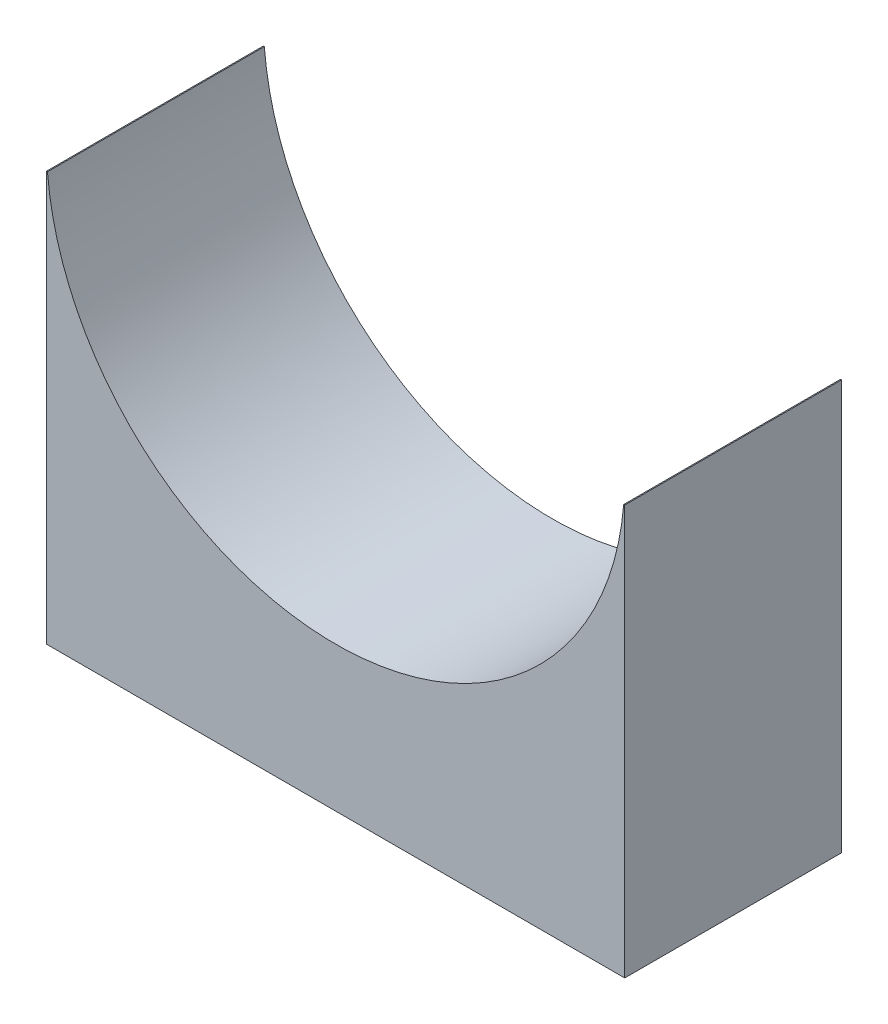
SolidWorks part; units mm, degrees
material "ABS"
ref_plane "Front Plane" through (0, 0, 0) normal (0, 0, 1) x (1, 0, 0)
ref_plane "Top Plane" through (0, 0, 0) normal (0, 1, 0) x (1, 0, 0)
ref_plane "Right Plane" through (0, 0, 0) normal (1, 0, 0) x (0, 0, -1)
ref_plane "Plane1" through (0, 0, 5) normal (0, 0, 1) x (1, 0, 0)
sketch "Sketch1" plane through (0, 0, 5) normal (0, 0, 1) x (1, 0, 0)
  line L0 (0, 25) -> (0, 0)
  line L1 (0, 0) -> (70, 0)
  line L2 (70, 0) -> (70, 25)
  line L3 (70, 25) -> (0, 25)
extrude "Boss-Extrude1" [suppressed] add sketch "Sketch1" against normal blind 5
sketch "Sketch2" [suppressed] plane through (0, 0, 5) normal (0, 0, 1) x (1, 0, 0)
  line L0 (38.9, 0) -> (38.9, 11)
  line L1 (21.1, 11) -> (21.1, 0)
  line L2 (21.1, 0) -> (38.9, 0)
  arc A0 (38.9, 11) -> (21.1, 11) centre (30, 11) ccw
extrude "Cut-Extrude1" [suppressed] cut sketch "Sketch2" against normal blind 0.5
sketch "Sketch3" [suppressed] plane through (0, 0, 0) normal (0, 0, -1) x (-1, 0, 0)
  line L0 (-36, 0) -> (-24, 0)
  line L1 (-24, 0) -> (-24, 11)
  line L2 (-36, 11) -> (-36, 0)
  arc A0 (-24, 11) -> (-36, 11) centre (-30, 11) ccw
extrude "Cut-Extrude2" [suppressed] cut sketch "Sketch3" against normal through all
sketch "Sketch4" [suppressed] plane through (0, 0, 0) normal (0, 0, -1) x (-1, 0, 0)
  line L0 (0, 8.5) -> (0, 13.5)
  line L1 (0, 13.5) -> (-9, 13.5)
  line L2 (-9, 8.5) -> (0, 8.5)
  arc A0 (-9, 13.5) -> (-9, 8.5) centre (-9, 11) ccw
extrude "Cut-Extrude3" [suppressed] cut sketch "Sketch4" against normal through all
sketch "Sketch5" [suppressed] plane through (0, 0, 0) normal (0, 0, -1) x (-1, 0, 0)
  line L0 (-52, 13.5) -> (-60, 13.5)
  line L1 (-60, 8.5) -> (-52, 8.5)
  arc A0 (-60, 13.5) -> (-60, 8.5) centre (-60, 11) ccw
  arc A1 (-52, 8.5) -> (-52, 13.5) centre (-52, 11) ccw
extrude "Cut-Extrude4" [suppressed] cut sketch "Sketch5" against normal through all
sketch "Sketch6" [suppressed] plane through (0, 0, 5) normal (0, 0, 1) x (1, 0, 0)
  line L0 (69, 5.5) -> (69, 19.5)
  line L1 (64.2, 19.5) -> (64.2, 5.5)
  arc A0 (64.2, 5.5) -> (69, 5.5) centre (66.6, 5.5) ccw
  arc A1 (69, 19.5) -> (64.2, 19.5) centre (66.6, 19.5) ccw
extrude "Cut-Extrude5" [suppressed] cut sketch "Sketch6" against normal blind 3
sketch "Sketch7" [suppressed] plane through (0, 0, 5) normal (0, 0, 1) x (1, 0, 0)
  line L0 (47.7, 5.5) -> (47.7, 19.5)
  line L1 (40.9, 19.5) -> (40.9, 5.5)
  arc A0 (40.9, 5.5) -> (47.7, 5.5) centre (44.3, 5.5) ccw
  arc A1 (47.7, 19.5) -> (40.9, 19.5) centre (44.3, 19.5) ccw
extrude "Cut-Extrude6" [suppressed] cut sketch "Sketch7" against normal blind 3
sketch "Sketch8" [suppressed] plane through (0, 0, 5) normal (0, 0, 1) x (1, 0, 0)
  line L0 (19.1, 5.5) -> (19.1, 19.5)
  line L1 (13.3, 19.5) -> (13.3, 5.5)
  arc A0 (13.3, 5.5) -> (19.1, 5.5) centre (16.2, 5.5) ccw
  arc A1 (19.1, 19.5) -> (13.3, 19.5) centre (16.2, 19.5) ccw
extrude "Cut-Extrude7" [suppressed] cut sketch "Sketch8" against normal blind 3
fillet "Fillet1" [suppressed] radius 1 tangent propagation no
sketch "Sketch9" plane through (0, 0, 0) normal (0, 0, 1) x (1, 0, 0)
  line L0 (-6, 0.5) -> (-5.9791, 0.5)
  line L1 (-6, 8) -> (6, 8)
  line L2 (-6, 8) -> (-6, -8)
  line L3 (-6, -8) -> (6, -8)
  line L4 (6, 8) -> (6, -8)
  line L5 (-6, -0.5) -> (-5.9791, -0.5)
  line L6 (5.9791, 0.5) -> (6, 0.5)
  line L7 (5.9791, -0.5) -> (6, -0.5)
  line L8 (-5.9896, 0.5) -> (-5.9896, -0.5) construction
  line L9 (-5.9896, 0) -> (-6, 0) construction
  line L10 (6, 8) -> (-6, -8) construction
  line L11 (-6, -8) -> (-6, -9)
  line L12 (-6, -9) -> (6, -9)
  line L13 (6, -9) -> (6, -8)
  line L14 (-6, 8) -> (-6, 9)
  line L15 (-6, 9) -> (6, 9)
  line L16 (6, 9) -> (6, 8)
  circle A0 centre (0, 0) radius 6
  circle A1 centre (0, 0) radius 8 construction
  point P20 (0, 0)
  dimension "D1" = 12
  dimension "D2" = 16
  dimension "D3" = 1
  dimension "D4" = 1
extrude "Boss-Extrude2" [suppressed] add sketch "Sketch9" along normal blind 4.5 contours A0 L5 L2 L3 L4 L7
extrude "Boss-Extrude3" add sketch "Sketch9<3>" along normal blind 4.5 contours A0 L5 L2 L3 L4 L7 | L12 L13 L3 L11 region at (0, -6.0845, 0) region at (0, -8.5, 0)
sketch "Sketch9<3>" plane through (0, 0, 0) normal (0, 0, 1) x (1, 0, 0) same geometry as "Sketch9"
